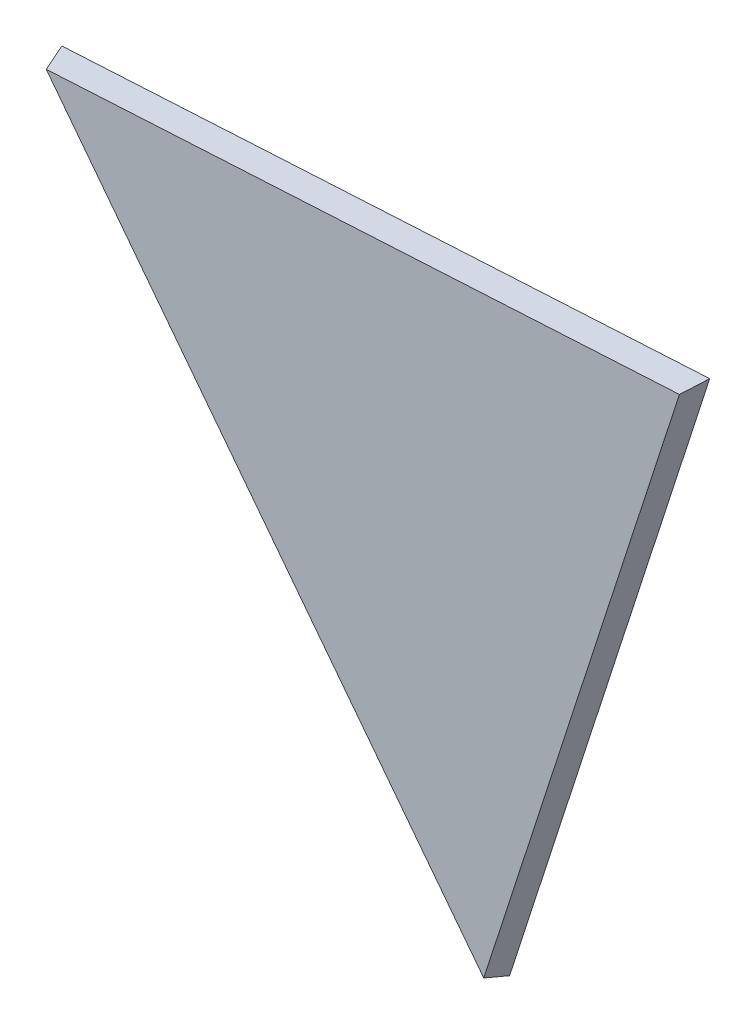
SolidWorks part; units mm, degrees
ref_plane "Спереди" through (0, 0, 0) normal (0, 0, 1) x (1, 0, 0)
ref_plane "Сверху" through (0, 0, 0) normal (0, 1, 0) x (1, 0, 0)
ref_plane "Справа" through (0, 0, 0) normal (1, 0, 0) x (0, 0, -1)
sketch "Эскиз1" plane through (0, 0, 0) normal (0, 0, 1) x (1, 0, 0)
  line L0 (-849.5899, 515.839) -> (787.506, 606.4051)
  line L1 (787.506, 606.4051) -> (281.6156, -953.1975)
  line L2 (281.6156, -953.1975) -> (-849.5899, 515.839)
extrude "Бобышка-Вытянуть1" add sketch "Эскиз1" along normal blind 60
chamfer "Chamfer3" distance 60 angle 11.23 1 edges at (-31.0419, 561.122, 60) first distance on face at (-31.0419, 561.122, 30)
chamfer "Chamfer4" distance 60 angle 11.23 1 edges at (532.5904, -179.4708, 60) first distance on face at (533.5756, -176.4335, 30)
chamfer "Chamfer5" distance 60 angle 9.015 1 edges at (-283.9872, -218.6793, 60) first distance on face at (-283.9872, -218.6793, 30)
equation "\"D1@Бобышка-Вытянуть1\" = \"THI@Geocorkwithdoor1.0.SLDASM\""
equation "\"D1@Chamfer1\"=\"THI@Geocorkwithdoor1.0.SLDASM\""
equation "\"D2@Chamfer1\"=\"AAchanferangle@Geocorkwithdoor1.0.SLDASM\""
equation "\"D1@Chamfer2\"=\"THI@Geocorkwithdoor1.0.SLDASM\""
equation "\"D2@Chamfer2\"=\"ABchanferAngle@Geocorkwithdoor1.0.SLDASM\""
equation "\"D1@Chamfer3\"=\"THI@Geocorkwithdoor1.0.SLDASM\""
equation "\"D2@Chamfer3\"=\"ABchanferAngle@Geocorkwithdoor1.0.SLDASM\""
equation "\"D1@Chamfer4\"=\"THI@Geocorkwithdoor1.0.SLDASM\""
equation "\"D2@Chamfer4\"=\"ABchanferAngle@Geocorkwithdoor1.0.SLDASM\""
equation "\"D1@Chamfer5\"=\"THI@Geocorkwithdoor1.0.SLDASM\""
equation "\"D2@Chamfer5\"=\"AAchanferangle@Geocorkwithdoor1.0.SLDASM\""
